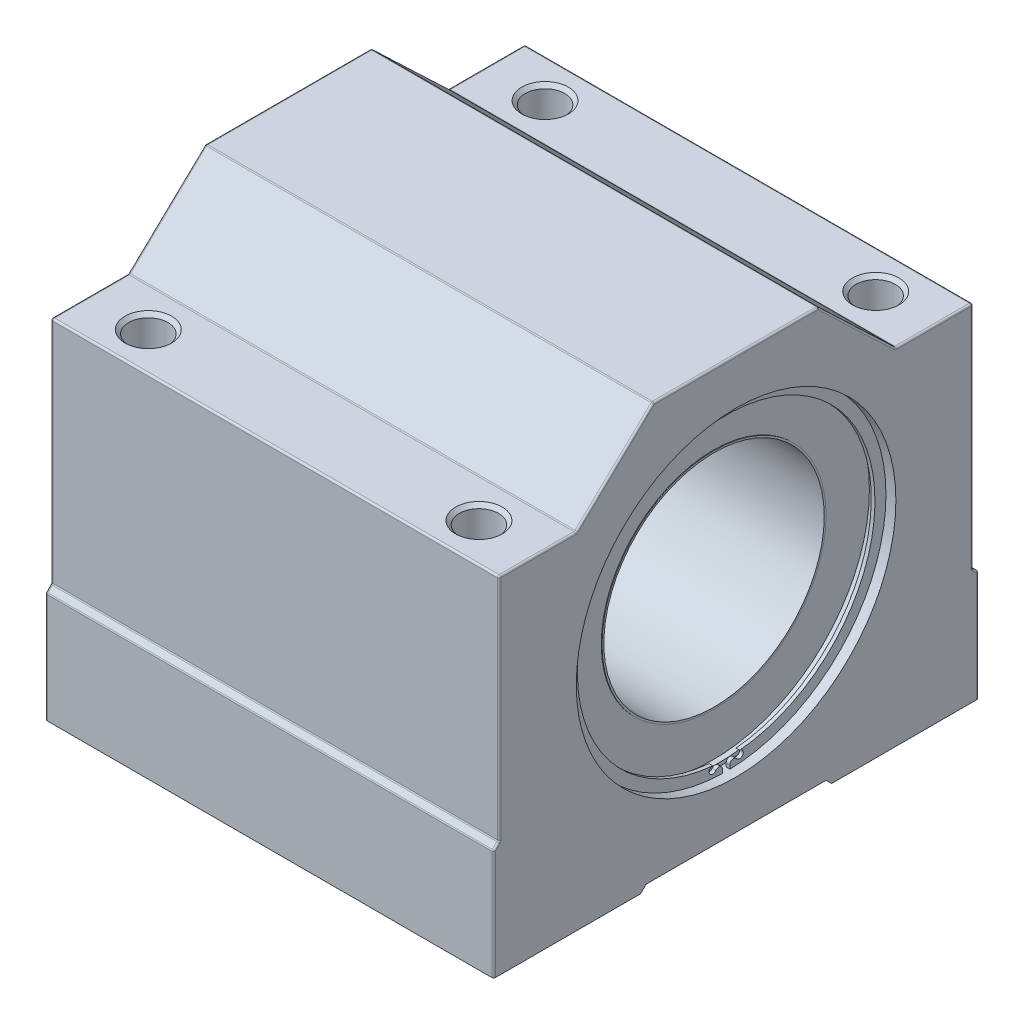
SolidWorks part; units mm, degrees
ref_plane "Front Plane" through (0, 0, 0) normal (0, 0, 1) x (1, 0, 0)
ref_plane "Top Plane" through (0, 0, 0) normal (0, 1, 0) x (1, 0, 0)
ref_plane "Right Plane" through (0, 0, 0) normal (1, 0, 0) x (0, 0, -1)
sketch "Sketch1" plane through (0, 0, 0) normal (1, 0, 0) x (0, 0, -1)
  line L1 (-26, -58) -> (-24.5, -56.5)
  line L2 (-24.5, -56.5) -> (24.5, -56.5)
  line L3 (24.5, -56.5) -> (26, -58)
  line L4 (26, -58) -> (66, -58)
  line L6 (66, -28) -> (64.5, -26.5)
  line L8 (64.5, 36) -> (43.5, 36)
  line L9 (43.5, 36) -> (22.5, 56)
  line L10 (22.5, 56) -> (-22.5, 56)
  line L11 (-22.5, 56) -> (-43.5, 36)
  line L12 (-43.5, 36) -> (-64.5, 36)
  line L15 (-66, -28) -> (-66, -58)
  line L16 (0, -56.5) -> (0, 56) construction
  line L17 (-16.278, 0) -> (14.0247, 0) construction
  line L18 (-66, -58) -> (-26, -58)
  line L19 (66, -28) -> (66, -58)
  line L20 (-64.5, -26.5) -> (-64.5, 36)
  line L21 (64.5, -26.5) -> (64.5, 36)
  line L22 (-54, 36) -> (-54, -58) construction
  line L23 (-54, -58) -> (54, 36) construction
  line L24 (54, 36) -> (54, -58) construction
  line L25 (-66, -28) -> (-64.5, -26.5)
  line L26 (-43.5, 0) -> (43.5, 0) construction
  circle A0 centre (0, 0) radius 43.5
  circle A1 centre (0, 0) radius 42.5
  circle A2 centre (0, 0) radius 30
  point P18 (0, 56)
  dimension "D12" = 60
  dimension "D1" = 132
  dimension "D2" = 94
  dimension "D3" = 58
  dimension "D5" = 114
  dimension "D6" = 108
  dimension "D4" = 30
  dimension "D7" = 1.5
  dimension "D8" = 45
  dimension "D9" = 1.5
  dimension "D10" = 40
  dimension "D11" = 1
extrude "Boss-Extrude1" add sketch "Sketch1" along normal blind 122 contours L25 L15 L18 L1 L2 L3 L4 L19 L6 L21 L8 L9 L10 L11 L12 L20 A0 region at (0, -56.2559, 46)
extrude "Extrude-Thin1" add sketch "Sketch1<4>" along normal blind 115.5 from offset 0.5 separate body thin contours A2 thin type one direction wall 0.5
sketch "Sketch1<4>" plane through (0, 0, 0) normal (1, 0, 0) x (0, 0, -1) same geometry as "Sketch1"
extrude "Boss-Extrude2" add sketch "Sketch1<5>" along normal blind 115 from offset 0.8 contours A1 A2 region at (0, 0, 41.2979)
sketch "Sketch1<5>" plane through (0, 0, 0) normal (1, 0, 0) x (0, 0, -1) same geometry as "Sketch1"
extrude "Boss-Extrude3" add sketch "Sketch1<6>" along normal blind 117 from offset 0.3 contours A0 A1 region at (0, 0, 43.377)
sketch "Sketch1<6>" plane through (0, 0, 0) normal (1, 0, 0) x (0, 0, -1) same geometry as "Sketch1"
ref_plane "Plane1" through (117.3, 0, 0) normal (1, 0, 0) x (0, 0, -1)
sketch "Sketch3" plane through (117.3, 0, 0) normal (1, 0, 0) x (0, 0, -1)
  line L0 (0, 0) -> (0, -50000) construction
  line L1 (-1.0006, -42.4882) -> (-1.0242, -43.4879)
  line L2 (1.0006, -42.4882) -> (1.0242, -43.4879)
  circle A0 centre (0, 0) radius 43.5 construction
  arc A1 (1.0242, -43.4879) -> (-1.0242, -43.4879) centre (0, 0) ccw
  circle A2 centre (0, 0) radius 42.5 construction
  arc A3 (0, -42.5) -> (1.0006, -42.4882) centre (0, 0) ccw
  arc A4 (-1.0006, -42.4882) -> (-2.8303, -41.8956) centre (-2, -42.4529) ccw
  circle A5 centre (-2, -42.4529) radius 0.25
  arc A6 (-2.2497, -42.4404) -> (-1.7502, -42.4639) centre (0, 0) ccw
  arc A7 (-2.8303, -41.8956) -> (-3.6584, -40.3382) centre (-3.6606, -41.3382) cw
  arc A8 (2.8303, -41.8956) -> (3.6584, -40.3382) centre (3.6606, -41.3382) ccw
  circle A10 centre (2, -42.4529) radius 0.25
  arc A11 (1.0006, -42.4882) -> (2.8303, -41.8956) centre (2, -42.4529) cw
  arc A13 (3.6584, -40.3382) -> (-3.6584, -40.3382) centre (0, 0) ccw
  dimension "D1" = 0.5
  dimension "D2" = 2
  dimension "D3" = 1
  dimension "D4" = 2
extrude "Boss-Extrude4" add sketch "Sketch3" along normal blind 1 from offset 1 contours A11 A8 A13 A7 A4 L1 A1 L2
fillet "Fillet1" radius 0.5 32 edges at (61, -26.5, -64.5) (61, -26.5, 64.5) (61, -28, 66) (61, -28, -66) (61, 36, -43.5) (61, 36, 43.5) (61, 56, 22.5) (61, 56, -22.5) (61, 36, -64.5) (61, 36, 64.5) (122, 46, -33) (122, 46, 33) (122, 4.75, 64.5) (0, -27.25, 65.25) (0, 46, 33) (122, -27.25, -65.25) (122, -43, -66) (122, 4.75, -64.5) (122, 56, 0) (122, 36, -54) (122, 36, 54) (122, -27.25, 65.25) (122, -43, 66) (0, -43, -66) (0, -27.25, -65.25) (0, 4.75, -64.5) (0, 46, -33) (0, 36, -54) (0, 56, 0) (0, -43, 66) (0, 4.75, 64.5) (0, 36, 54)
sketch "Sketch4" plane through (0, -58, 0) normal (0, -1, 0) x (1, 0, 0)
  line L0 (61, 66) -> (61, -66) construction
  line L1 (121.5, 66) -> (0.5, 66) construction
  line L2 (121.5, -66) -> (0.5, -66) construction
  line L4 (-4.9444, 54) -> (27.0918, 54) construction
  line L6 (0, 0) -> (36.1646, 0) construction
  circle A0 centre (16, 54) radius 5.35
  circle A1 centre (106, 54) radius 5.35
  circle A2 centre (106, -54) radius 5.35
  circle A3 centre (16, -54) radius 5.35
  dimension "D2" = 10.7
  dimension "D1" = 54
  dimension "D3" = 90
extrude "Cut-Extrude3" cut sketch "Sketch4" against normal through all
chamfer "Chamfer1" distance 1 angle 45 6 edges at (106, 36, -59.35) (16, 36, -59.35) (16, 36, 48.65) (106, 36, 48.65) (106, -58, 59.35) (16, -58, 48.65)
equation "\"D1@Boss-Extrude2\"= \"D1@Boss-Extrude1\" - 2 - 5"
equation "\"D1@Boss-Extrude3\"= \"D1@Boss-Extrude1\" - 5"
equation "\"D1@Sketch4\"= \"D6@Sketch1\" / 2"
equation "\"D1@Extrude-Thin1\"= \"D1@Boss-Extrude3\" - 1.5"
